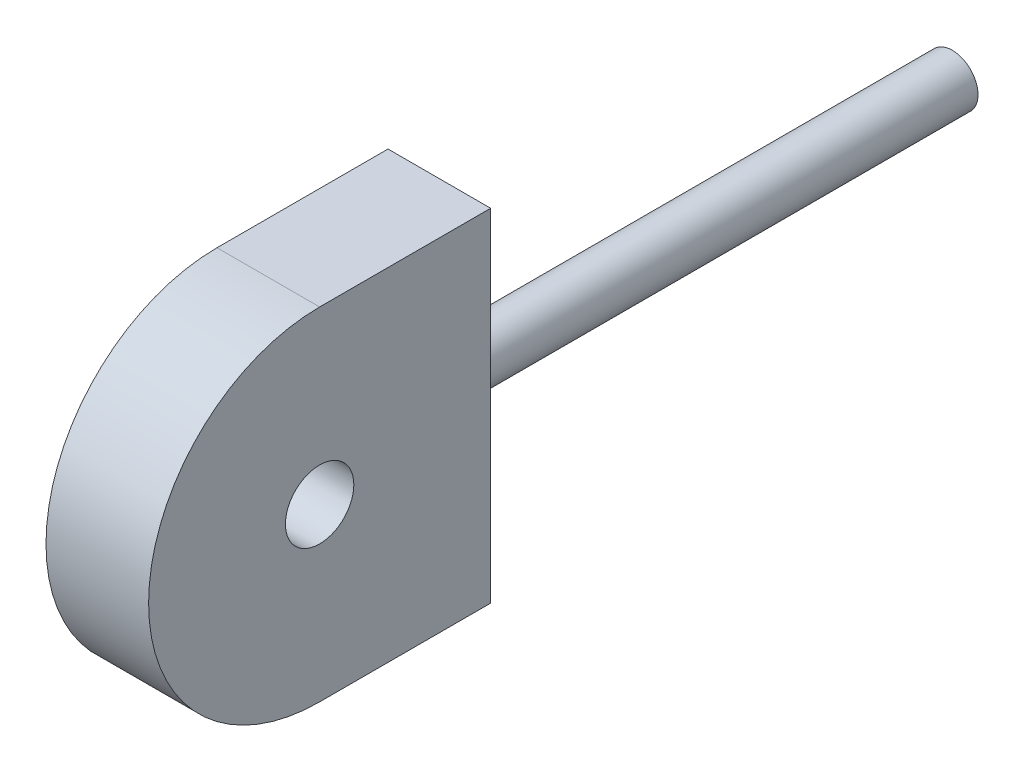
SolidWorks part; units mm, degrees
ref_plane "前视基准面" through (0, 0, 0) normal (0, 0, 1) x (1, 0, 0)
ref_plane "上视基准面" through (0, 0, 0) normal (0, 1, 0) x (1, 0, 0)
ref_plane "右视基准面" through (0, 0, 0) normal (1, 0, 0) x (0, 0, -1)
other "Configuration Table"
sketch "草图1" plane through (0, 0, 0) normal (1, 0, 0) x (0, 0, -1)
  line L7 (10, 10) -> (0, 10)
  line L8 (10, 10) -> (10, -10)
  line L9 (10, -10) -> (0, -10)
  line L10 (0, 10) -> (0, -10)
  circle A0 centre (0, 0) radius 10
  circle A2 centre (0, 0) radius 2
  point P0 (0, 0)
  point P1 (0, 0)
  point P10 (-20, 4.5816)
  point P12 (-20, -14.8063)
  dimension "D4" = 4
  dimension "D1" = 20
  dimension "D3" = 10
extrude "凸台-拉伸2" add sketch "草图1" along normal blind 3 and the other way blind 3 contours A2 L10 A0 | A2 L10 A0 | A0 L8 L7 | A0 L9 L8 region at (0, 7.7663, -7.7663) region at (0, 0, -4.3856) region at (0, 0, 4.3856) region at (0, -7.7663, -7.7663)
sketch "草图2" plane through (0, 0, -10) normal (0, 0, -1) x (-1, 0, 0)
  circle A0 centre (0, 0) radius 1.5
  dimension "D1" = 3
extrude "凸台-拉伸3" add sketch "草图2" along normal blind 30
